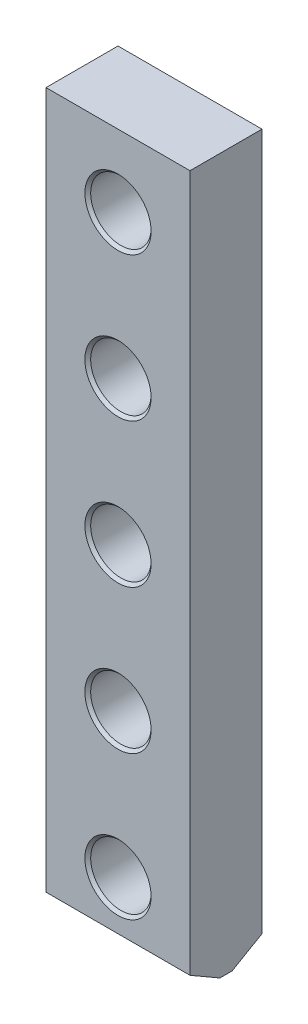
SolidWorks part; units mm, degrees
material "Простая углеродистая сталь"
ref_plane "Спереди" through (0, 0, 0) normal (0, 0, 1) x (1, 0, 0)
ref_plane "Сверху" through (0, 0, 0) normal (0, 1, 0) x (1, 0, 0)
ref_plane "Справа" through (0, 0, 0) normal (1, 0, 0) x (0, 0, -1)
sketch "Эскиз1" plane through (0, 0, 0) normal (0, 0, 1) x (1, 0, 0)
  line L1 (0, 0) -> (50, 0)
  line L2 (0, 0) -> (0, 248)
  line L3 (0, 248) -> (50, 248)
  line L4 (50, 0) -> (50, 248)
  point P5 (25, 248)
  dimension "D1" = 248
  dimension "D2" = 50
extrude "Бобышка-Вытянуть1" add sketch "Эскиз1" along normal blind 25
sketch "Эскиз2" plane through (0, 0, 25) normal (0, 0, 1) x (1, 0, 0)
  line L0 (0, 0) -> (50, 0) construction
  line L1 (50, 0) -> (50, 248) construction
  circle A0 centre (25, 23) radius 10.5
  circle A1 centre (25, 73) radius 10.5
  circle A2 centre (25, 123) radius 10.5
  circle A3 centre (25, 173) radius 10.5
  circle A4 centre (25, 223) radius 10.5
  dimension "D1" = 5
  dimension "D2" = 23
  dimension "D3" = 25
  dimension "D4" = 21
extrude "Вырез-Вытянуть1" cut sketch "Эскиз2" against normal through all
chamfer "Фаска1" distance 6 angle 60 1 edges at (25, 0, 0) first distance on face at (35.5, 73, 0)
chamfer "Фаска2" distance 6 angle 60 1 edges at (25, 0, 25) first distance on face at (35.5, 73, 25)
chamfer "Фаска3" distance 1 angle 45 10 edges at (35.5, 223, 0) (35.5, 23, 0) (35.5, 73, 0) (35.5, 123, 0) (35.5, 173, 0) (35.5, 23, 25) (35.5, 73, 25) (35.5, 223, 25) (35.5, 173, 25) (35.5, 123, 25)
